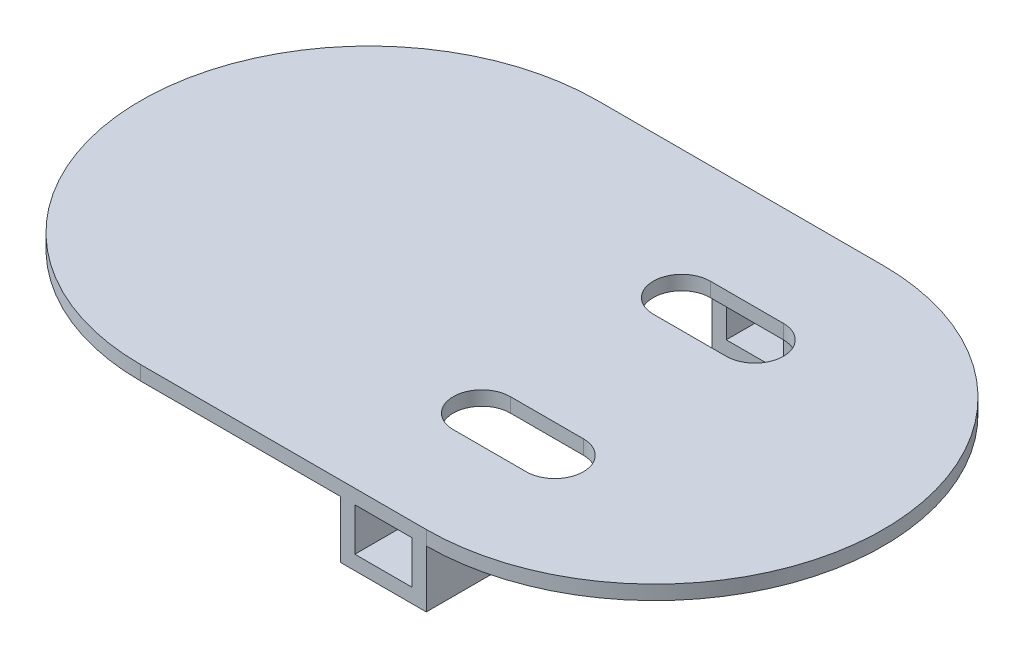
SolidWorks part; units mm, degrees
ref_plane "Front Plane" through (0, 0, 0) normal (0, 0, 1) x (1, 0, 0)
ref_plane "Top Plane" through (0, 0, 0) normal (0, 1, 0) x (1, 0, 0)
ref_plane "Right Plane" through (0, 0, 0) normal (1, 0, 0) x (0, 0, -1)
sketch "Sketch1" plane through (0, 0, 0) normal (0, 1, 0) x (1, 0, 0)
  line L1 (-50, 0) -> (50, 0) construction
  line L6 (-50, 80) -> (50, 80)
  line L7 (-50, -80) -> (50, -80)
  arc A0 (-50, 80) -> (-50, -80) centre (-50, 0) ccw
  arc A1 (50, -80) -> (50, 80) centre (50, 0) ccw
  point P2 (0, 0)
  dimension "D2" = 80
  dimension "D1" = 100
extrude "Boss-Extrude2" add sketch "Sketch1" along normal blind 5 contours A1 L6 A0 L7
sketch "Sketch4" plane through (0, 0, 0) normal (0, -1, 0) x (1, 0, 0)
  line L0 (50, 80) -> (20, 80)
  line L1 (50, 80) -> (50, 50)
  line L2 (20, 80) -> (20, 50)
  line L3 (50, 50) -> (20, 50)
  line L4 (-50, 80) -> (50, 80) construction
  dimension "D1" = 30
  dimension "D2" = 30
extrude "Boss-Extrude3" add sketch "Sketch4" along normal blind 20
sketch "Sketch5" plane through (0, 0, 80) normal (0, 0, 1) x (1, 0, 0)
  line L0 (50, -20) -> (20, -20) construction
  line L1 (25, -15) -> (45, -15)
  line L2 (25, -15) -> (25, 0)
  line L3 (25, 0) -> (45, 0)
  line L4 (45, -15) -> (45, 0)
  line L5 (25, -15) -> (45, 0) construction
  line L6 (25, 0) -> (45, -15) construction
  line L7 (50, -20) -> (50, 0) construction
  line L8 (20, -20) -> (20, 0) construction
  point P0 (35, -7.5)
  dimension "D1" = 5
  dimension "D2" = 5
  dimension "D3" = 5
  dimension "D4" = 15
extrude "Cut-Extrude1" cut sketch "Sketch5" against normal through all
sketch "Sketch9" plane through (0, 5, 0) normal (0, 1, 0) x (1, 0, 0)
  line L0 (50, -35) -> (24.4313, -35) construction
  line L1 (50, -45) -> (24.4313, -45)
  line L2 (50, -25) -> (24.4313, -25)
  line L5 (-50, -80) -> (50, -80) construction
  arc A0 (50, -45) -> (50, -25) centre (50, -35) ccw
  arc A1 (24.4313, -25) -> (24.4313, -45) centre (24.4313, -35) ccw
  point P2 (37.2157, -35)
  dimension "D2" = 10
  dimension "D1" = 45
extrude "Cut-Extrude2" cut sketch "Sketch9" against normal blind 20
mirror "Mirror1" about plane through (0, 0, 0) normal (0, 0, 1) of "Cut-Extrude2", "Cut-Extrude1", "Boss-Extrude3"
